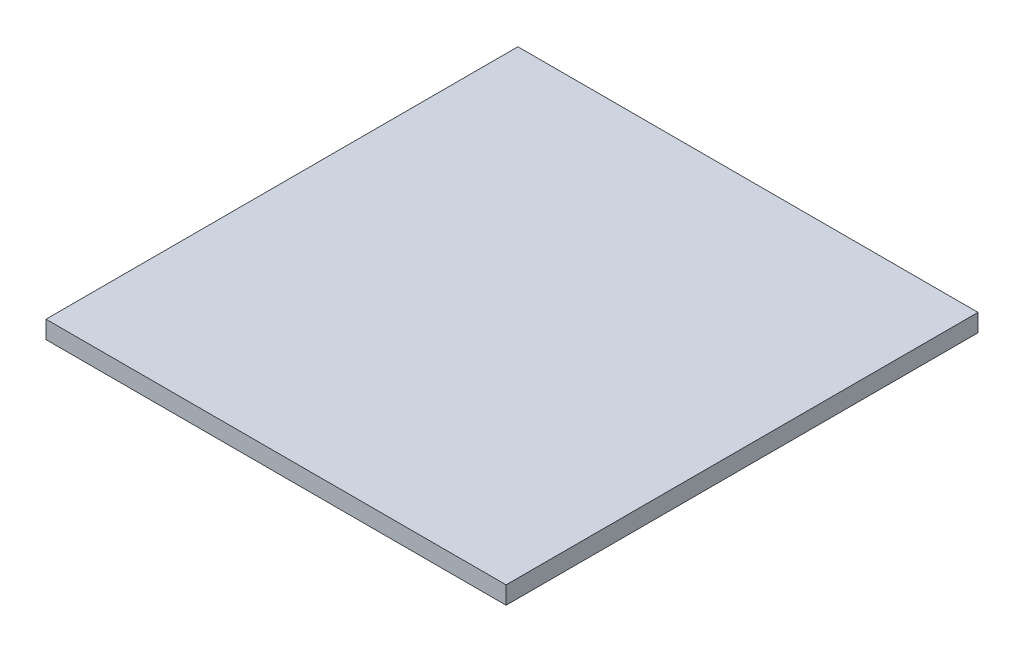
SolidWorks part; units mm, degrees
ref_plane "Front" through (0, 0, 0) normal (0, 0, 1) x (1, 0, 0)
ref_plane "Top" through (0, 0, 0) normal (0, 1, 0) x (1, 0, 0)
ref_plane "Right" through (0, 0, 0) normal (1, 0, 0) x (0, 0, -1)
sketch "Sketch1" plane through (0, 0, 0) normal (0, 1, 0) x (1, 0, 0)
  line L1 (-247.65, 254) -> (247.65, 254)
  line L2 (-247.65, 254) -> (-247.65, -254)
  line L3 (-247.65, -254) -> (247.65, -254)
  line L4 (247.65, 254) -> (247.65, -254)
  line L5 (-247.65, 254) -> (247.65, -254) construction
  line L6 (-247.65, -254) -> (247.65, 254) construction
  point P0 (0, 0)
  dimension "D1" = 495.3
  dimension "D2" = 508
extrude "Boss-Extrude1" add sketch "Sketch1" along normal blind 19.05
sketch "Sketch2" [suppressed] plane through (0, 19.05, 0) normal (0, 1, 0) x (1, 0, 0)
  line L0 (-254, 254) -> (-254, 215.9) construction
  line L1 (-254, 254) -> (-254, -254) construction
  line L2 (-254, 215.9) -> (-215.9, 215.9) construction
  line L3 (-215.9, 215.9) -> (-215.9, 254) construction
  line L4 (254, 254) -> (-254, 254) construction
  line L5 (-215.9, 254) -> (-254, 254) construction
  line L7 (-241.3, 241.3) -> (-190.5, 241.3)
  line L8 (-241.3, 241.3) -> (-241.3, 190.5)
  line L9 (-241.3, 190.5) -> (-190.5, 190.5)
  line L10 (-190.5, 241.3) -> (-190.5, 190.5)
  line L11 (-241.3, 241.3) -> (-190.5, 190.5) construction
  line L12 (-241.3, 190.5) -> (-190.5, 241.3) construction
  dimension "D1" = 50.8
  dimension "D2" = 50.8
  dimension "D3" = 12.7
extrude "Cut-Extrude1" [suppressed] cut sketch "Sketch2" against normal through all
pattern_linear "LPattern1" [suppressed] count 8 spacing 60.325 count 8 spacing 60.325 of bodies 180
